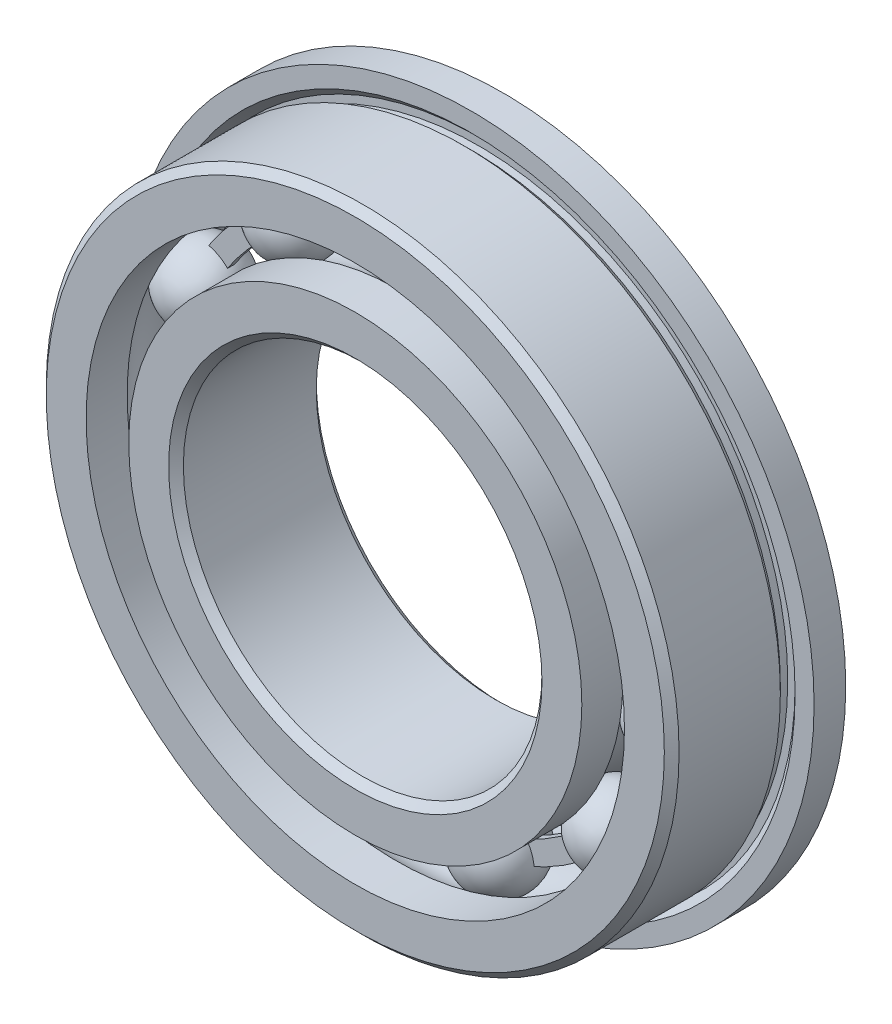
SolidWorks part; units mm, degrees
ref_plane "Front Plane" through (0, 0, 0) normal (0, 0, 1) x (1, 0, 0)
ref_plane "Top Plane" through (0, 0, 0) normal (0, 1, 0) x (1, 0, 0)
ref_plane "Right Plane" through (0, 0, 0) normal (1, 0, 0) x (0, 0, -1)
sketch "Sketch1" plane through (0, 0, 0) normal (1, 0, 0) x (0, 0, -1)
  line L0 (-3.5, 0) -> (3.5, 0) construction
  line L1 (0, 15) -> (0, -15) construction
  line L2 (3.15, 15) -> (-3.15, 15) construction
  line L3 (-3.15, 15) -> (-3.5, 14.65)
  line L4 (-3.5, 14.65) -> (-3.5, 12.761)
  line L5 (-3.5, 12.761) -> (-1.5556, 12.761)
  line L6 (3.5, 12.761) -> (1.5556, 12.761)
  line L7 (3.5, 14.65) -> (3.5, 12.761)
  line L8 (3.15, 15) -> (3.5, 14.65) construction
  line L9 (0, 15) -> (0, 11.75) construction
  line L10 (0, 11.75) -> (0, 8.5) construction
  line L11 (2, 0) -> (2, 15) construction
  line L12 (3.5, 14.65) -> (3.5, 16.25)
  line L13 (3.5, 16.25) -> (2, 16.25)
  line L14 (2, 16.25) -> (2, 15.35)
  line L15 (2, 15.35) -> (2.35, 15)
  line L16 (2.35, 15) -> (2.35, 14.65)
  line L17 (2.35, 14.65) -> (2, 14.65)
  line L18 (2, 14.65) -> (1.65, 15)
  line L19 (-3.15, 15) -> (1.65, 15)
  line L20 (3.5, 16.25) -> (3.5, -16.25) construction
  line L21 (2, 15) -> (2, 15.35) construction
  line L22 (2, 15) -> (1.65, 15) construction
  arc A0 (-1.5556, 12.761) -> (1.5556, 12.761) centre (0, 11.75) cw
  point P14 (0, 8.5)
  point P15 (2, 0)
  point P25 (3.5, 0)
  dimension "Width" = 7
  dimension "OD" = 30
  dimension "D1" = 45
  dimension "D2" = 0.35
  dimension "ID" = 17
  dimension "D3" = 3.1111
  dimension "D4" = 1.011
  dimension "Th" = 1.5
  dimension "Flange OD" = 32.5
revolve "Revolve1" add sketch "Sketch1" angle 360 about L0
sketch "Sketch3" plane through (0, 0, 0) normal (1, 0, 0) x (0, 0, -1)
  line L0 (-3.5, 10.739) -> (-1.5556, 10.739)
  line L1 (0, 15) -> (0, -15) construction
  line L2 (-3.5, 14.65) -> (-3.5, 12.761) construction
  line L3 (-3.5, 10.739) -> (-3.5, 8.85)
  line L4 (-3.15, 15) -> (-3.5, 14.65) construction
  line L5 (-3.5, 8.85) -> (-3.15, 8.5)
  line L6 (-3.15, 8.5) -> (3.15, 8.5)
  line L8 (3.15, 8.5) -> (3.5, 8.85)
  line L10 (3.5, 8.85) -> (3.5, 10.739)
  line L11 (3.5, 10.739) -> (1.5556, 10.739)
  line L13 (3.15, 15) -> (3.5, 14.65) construction
  arc A0 (1.5556, 12.761) -> (-1.5556, 12.761) centre (0, 11.75) ccw construction
  arc A1 (1.5556, 10.739) -> (-1.5556, 10.739) centre (0, 11.75) cw
revolve "Revolve3" add sketch "Sketch3" angle 360 about L0
sketch "Sketch6" plane through (0, 0, 0) normal (1, 0, 0) x (0, 0, -1)
  line L1 (-0.1685, 12.2555) -> (0.1685, 12.2555)
  line L2 (-0.1685, 12.2555) -> (-0.1685, 11.2445)
  line L3 (-0.1685, 11.2445) -> (0.1685, 11.2445)
  line L4 (0.1685, 12.2555) -> (0.1685, 11.2445)
  line L5 (-0.1685, 12.2555) -> (0.1685, 11.2445) construction
  line L6 (-0.1685, 11.2445) -> (0.1685, 12.2555) construction
  point P4 (0, 11.75)
  dimension "D1" = 1.011
  dimension "D2" = 0.337
revolve "Revolve6" add sketch "Sketch6" angle 360 about L0
sketch "Sketch4" plane through (0, 0, 0) normal (1, 0, 0) x (0, 0, -1)
  line L0 (-1.8552, 11.75) -> (1.8552, 11.75)
  arc A2 (-1.8552, 11.75) -> (1.8552, 11.75) centre (0, 11.75) cw
  arc A3 (1.5556, 12.761) -> (-1.5556, 12.761) centre (0, 11.75) ccw construction
revolve "Revolve4" add sketch "Sketch4" angle 360 about L0
ref_axis "Axis1" through (0, 0, -3.5) along (0, 0, 1)
pattern_circular "CirPattern1" count 11 every 32.727 about axis through (0, 0, -3.5) along (0, 0, 1) of bodies 104
sketch "Sketch5" plane through (0, 0, 0) normal (1, 0, 0) x (0, 0, -1)
  line L0 (-3.5, 12.761) -> (-1.5556, 12.761) construction
  line L1 (-3.325, 12.761) -> (-1.8552, 12.761)
  line L2 (-3.325, 12.761) -> (-3.325, 10.739)
  line L3 (-3.325, 10.739) -> (-1.8552, 10.739)
  line L4 (-1.8552, 12.761) -> (-1.8552, 10.739)
  line L5 (-3.5, 10.739) -> (-1.5556, 10.739) construction
  line L6 (3.5, 12.761) -> (1.5556, 12.761) construction
  line L7 (3.325, 12.761) -> (1.8552, 12.761)
  line L8 (3.325, 12.761) -> (3.325, 10.739)
  line L9 (3.325, 10.739) -> (1.8552, 10.739)
  line L10 (1.8552, 12.761) -> (1.8552, 10.739)
  line L11 (3.5, 10.739) -> (1.5556, 10.739) construction
  line L12 (-3.15, 15) -> (-3.5, 14.65) construction
  point P18 (-3.325, 14.825)
revolve "Revolve5" [suppressed] add sketch "Sketch5" angle 360 about L0
ref_axis "Center Axis 1" through (0, 0, -3.15) along (0, 0, 1)
ref_plane "Contact Plane 1" through (0, 0, -3.5) normal (0, 0, -1) x (-1, 0, 0)
ref_plane "Contact Plane 2" through (0, 0, -2) normal (0, 0, 1) x (1, 0, 0)
equation "\"D2@Sketch1\" = \"Width@Sketch1\"*.05"
equation "\"D3@Sketch1\" = \"Width@Sketch1\"/2.25"
equation "\"D4@Sketch1\" = (((\"OD@Sketch1\"-\"Width@Sketch1\")/2)/3.25)/3.5"
equation "\"D2@CirPattern1\" = 360/\"Balls@CirPattern1\""
equation "\"D1@Sketch6\"=\"D4@Sketch1\""
equation "\"D2@Sketch6\"=\"D1@Sketch6\"/3"
